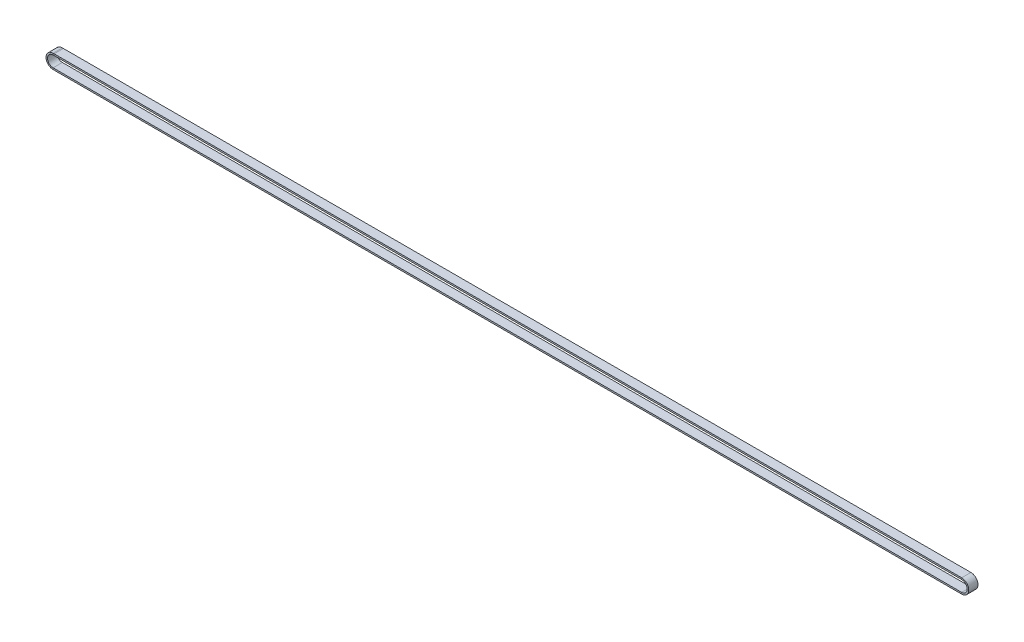
SolidWorks part; units mm, degrees
ref_plane "Front Plane" through (0, 0, 0) normal (0, 0, 1) x (1, 0, 0)
ref_plane "Top Plane" through (0, 0, 0) normal (0, 1, 0) x (1, 0, 0)
ref_plane "Right Plane" through (0, 0, 0) normal (1, 0, 0) x (0, 0, -1)
sketch "Sketch2" plane through (0, 0, -113.2334) normal (0, 0, 1) x (1, 0, 0)
  line L0 (0, 0) -> (1, 0) construction
  line L1 (0, 0) -> (0, 1) construction
  line L2 (-1, 79.0918) -> (883.5206, 79.0918)
  line L3 (883.5206, 65.2918) -> (-1, 65.2918)
  arc A0 (-1, 65.2918) -> (-1, 79.0918) centre (-1, 72.1918) cw
  arc A1 (883.5206, 79.0918) -> (883.5206, 65.2918) centre (883.5206, 72.1918) cw
sketch "Sketch3" plane through (0, 0, 0) normal (1, 0, 0) x (0, 0, -1)
  line L1 (113.2334, 77.5918) -> (104.2334, 77.5918)
  line L2 (113.2334, 77.5918) -> (113.2334, 79.0918)
  line L3 (113.2334, 79.0918) -> (104.2334, 79.0918)
  line L4 (104.2334, 77.5918) -> (104.2334, 79.0918)
  dimension "D1" = 9
  dimension "D2" = 1.5
sweep "Sweep1" add profiles "Sketch3" path "Sketch2"
